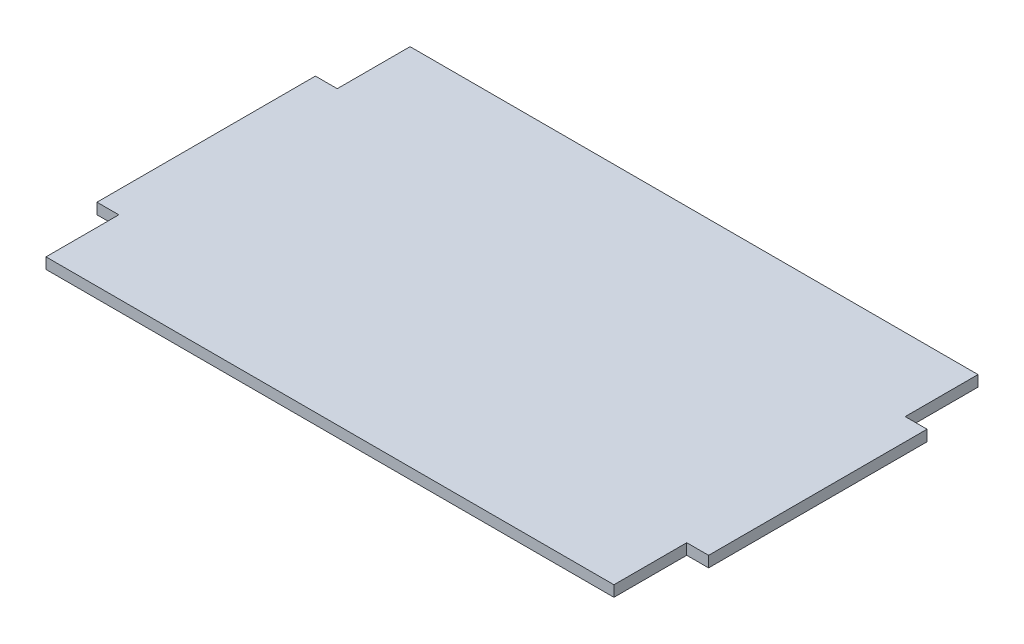
SolidWorks part; units mm, degrees
ref_plane "Front Plane" through (0, 0, 0) normal (0, 0, 1) x (1, 0, 0)
ref_plane "Top Plane" through (0, 0, 0) normal (0, 1, 0) x (1, 0, 0)
ref_plane "Right Plane" through (0, 0, 0) normal (1, 0, 0) x (0, 0, -1)
sketch "Sketch2" plane through (0, 0, 0) normal (0, 1, 0) x (1, 0, 0)
  line L0 (0, -50) -> (160, -50) construction
  line L1 (0, 0) -> (156, 0)
  line L2 (0, 0) -> (0, -20)
  line L3 (0, -100) -> (156, -100)
  line L4 (156, 0) -> (156, -20)
  line L5 (0, -20) -> (-6, -20)
  line L6 (78, 0) -> (78, -66.6608) construction
  line L7 (-6, -80) -> (-6, -20)
  line L8 (0, -80) -> (-6, -80)
  line L9 (156, -80) -> (162, -80)
  line L10 (156, -20) -> (162, -20)
  line L11 (162, -80) -> (162, -20)
  line L12 (0, -80) -> (0, -100)
  line L13 (156, -80) -> (156, -100)
  dimension "D1" = 100
  dimension "D2" = 168
  dimension "D3" = 6
  dimension "D4" = 168
extrude "Boss-Extrude1" add sketch "Sketch2" along normal blind 3
